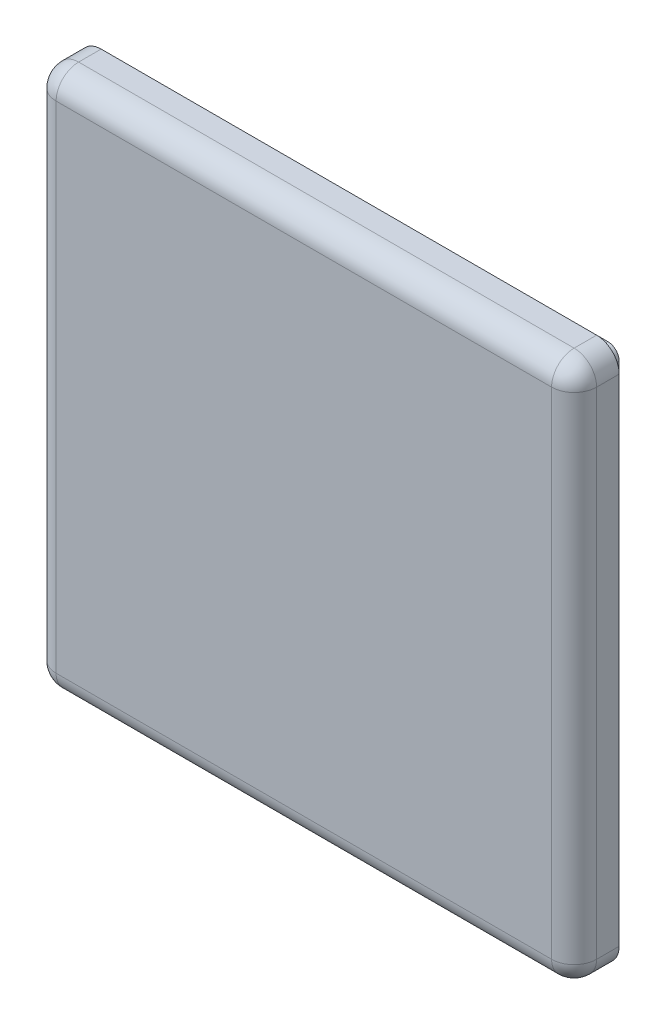
SolidWorks part; units mm, degrees
ref_plane "Front Plane" through (0, 0, 0) normal (0, 0, 1) x (1, 0, 0)
ref_plane "Top Plane" through (0, 0, 0) normal (0, 1, 0) x (1, 0, 0)
ref_plane "Right Plane" through (0, 0, 0) normal (1, 0, 0) x (0, 0, -1)
sketch "Sketch1" plane through (0, 0, 0) normal (0, 0, 1) x (1, 0, 0)
  line L1 (-12, -12) -> (12, -12)
  line L2 (-12, -12) -> (-12, 12)
  line L3 (-12, 12) -> (12, 12)
  line L4 (12, -12) -> (12, 12)
  line L5 (-12, -12) -> (12, 12) construction
  line L6 (-12, 12) -> (12, -12) construction
  point P0 (0, 0)
  dimension "D1" = 24
extrude "Boss-Extrude1" add sketch "Sketch1" along normal blind 2
sketch "Sketch2" plane through (0, 0, 0) normal (0, 0, -1) x (-1, 0, 0)
  line L1 (-11, 11) -> (11, 11)
  line L2 (-11, 11) -> (-11, -11)
  line L3 (-11, -11) -> (11, -11)
  line L4 (11, 11) -> (11, -11)
  line L5 (-11, 11) -> (11, -11) construction
  line L6 (-11, -11) -> (11, 11) construction
  line L7 (-10, 10) -> (10, 10)
  line L8 (-10, 10) -> (-10, -10)
  line L9 (-10, -10) -> (10, -10)
  line L10 (10, 10) -> (10, -10)
  line L11 (-10, 10) -> (10, -10) construction
  line L12 (-10, -10) -> (10, 10) construction
  point P0 (0, 0)
  point P5 (0, 0)
  dimension "D1" = 22
  dimension "D2" = 20
extrude "Boss-Extrude2" add sketch "Sketch2" along normal blind 1
fillet "Fillet1" radius 1 4 edges at (12, 0, 2) (0, -12, 2) (-12, 0, 2) (0, 12, 2)
fillet "Fillet2" radius 1 8 edges at (11.7071, 11.7071, 1.7071) (11.7071, -11.7071, 1.7071) (-11.7071, -11.7071, 1.7071) (-11.7071, 11.7071, 1.7071) (12, 12, 0.5) (12, -12, 0.5) (-12, -12, 0.5) (-12, 12, 0.5)
fillet "Fillet3" radius 0.5 4 edges at (-11, -11, -0.5) (-11, 11, -0.5) (11, 11, -0.5) (11, -11, -0.5)
